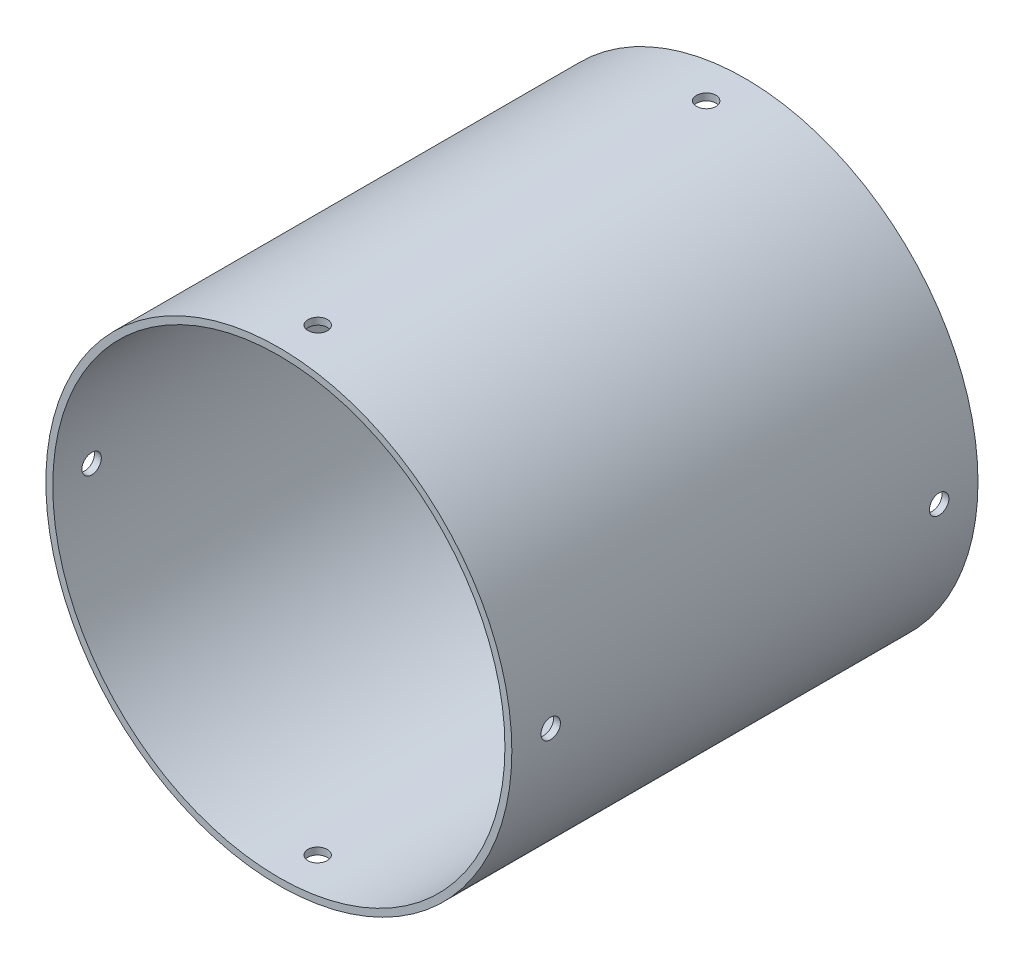
SolidWorks part; units mm, degrees
ref_plane "Front Plane" through (0, 0, 0) normal (0, 0, 1) x (1, 0, 0)
ref_plane "Top Plane" through (0, 0, 0) normal (0, 1, 0) x (1, 0, 0)
ref_plane "Right Plane" through (0, 0, 0) normal (1, 0, 0) x (0, 0, -1)
sketch "Sketch1" plane through (0, 0, 0) normal (0, 0, 1) x (1, 0, 0)
  circle A0 centre (0, 0) radius 76.1746
  circle A1 centre (0, 0) radius 73.914
  dimension "D1" = 152.3492
  dimension "D2" = 147.828
extrude "Boss-Extrude1" add sketch "Sketch1" along normal blind 152.4
ref_plane "Plane1" through (76.2, 0, 0) normal (1, 0, 0) x (0, 0, -1)
sketch "Sketch2" plane through (76.2, 0, 0) normal (1, 0, 0) x (0, 0, -1)
  line L0 (-152.4, 76.1746) -> (-152.4, -76.1746) construction
  line L1 (0, -76.1746) -> (0, 76.1746) construction
  circle A0 centre (-139.7, 0) radius 3.175
  circle A1 centre (-12.7, 0) radius 3.175
  dimension "D1" = 6.35
  dimension "D2" = 6.35
  dimension "D3" = 12.7
  dimension "D4" = 12.7
extrude "Cut-Extrude1" cut sketch "Sketch2" against normal blind 25.4
pattern_circular "CirPattern1" count 4 over 360 about axis through (0, 0, 152.4) along (0, 0, -1) of "Cut-Extrude1"
